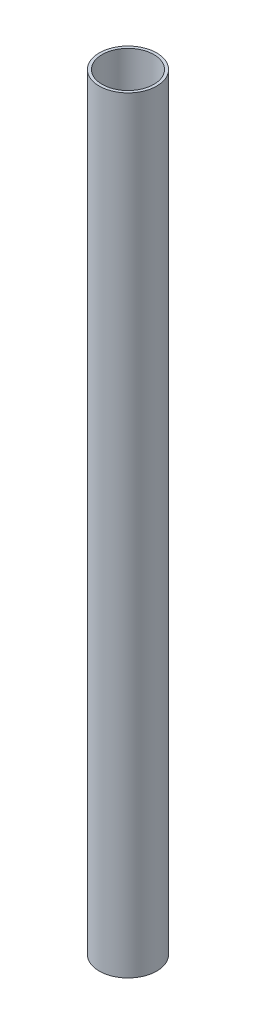
SolidWorks part; units mm, degrees
ref_plane "Front Plane" through (0, 0, 0) normal (0, 0, 1) x (1, 0, 0)
ref_plane "Top Plane" through (0, 0, 0) normal (0, 1, 0) x (1, 0, 0)
ref_plane "Right Plane" through (0, 0, 0) normal (1, 0, 0) x (0, 0, -1)
sketch "Sketch1" plane through (0, 0, 0) normal (0, 1, 0) x (1, 0, 0)
  circle A0 centre (0, 0) radius 15
  circle A1 centre (0, 0) radius 13.5
  dimension "D1" = 1.5
  dimension "D2" = 30
extrude "Boss-Extrude1" add sketch "Sketch1" along normal blind 400
ref_plane "Plane1" through (0, 0, 50) normal (0, 0, 1) x (1, 0, 0)
